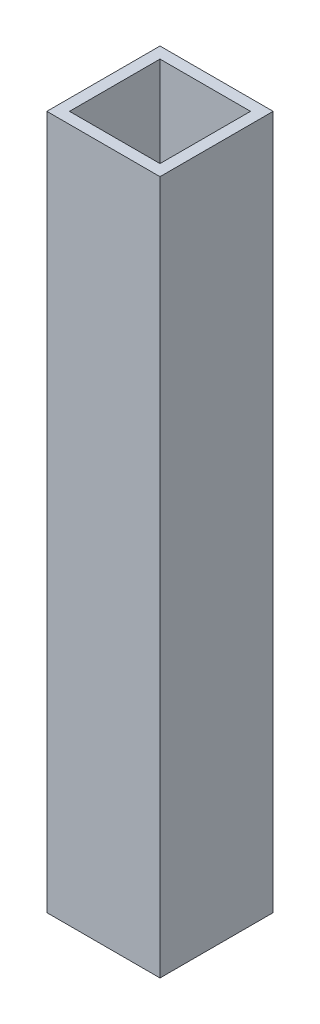
SolidWorks part; units mm, degrees
material "6061 Alloy"
ref_plane "Front Plane" through (0, 0, 0) normal (0, 0, 1) x (1, 0, 0)
ref_plane "Top Plane" through (0, 0, 0) normal (0, 1, 0) x (1, 0, 0)
ref_plane "Right Plane" through (0, 0, 0) normal (1, 0, 0) x (0, 0, -1)
sketch "Sketch1" plane through (0, 0, 0) normal (0, 1, 0) x (1, 0, 0)
  line L1 (0, 0) -> (15, 0)
  line L2 (0, 0) -> (0, 15)
  line L3 (0, 15) -> (15, 15)
  line L4 (15, 0) -> (15, 15)
  dimension "D1" = 15
extrude "Extrude-Thin1" add sketch "Sketch1" along normal blind 92 thin thin type one direction reverse wall 1.5
